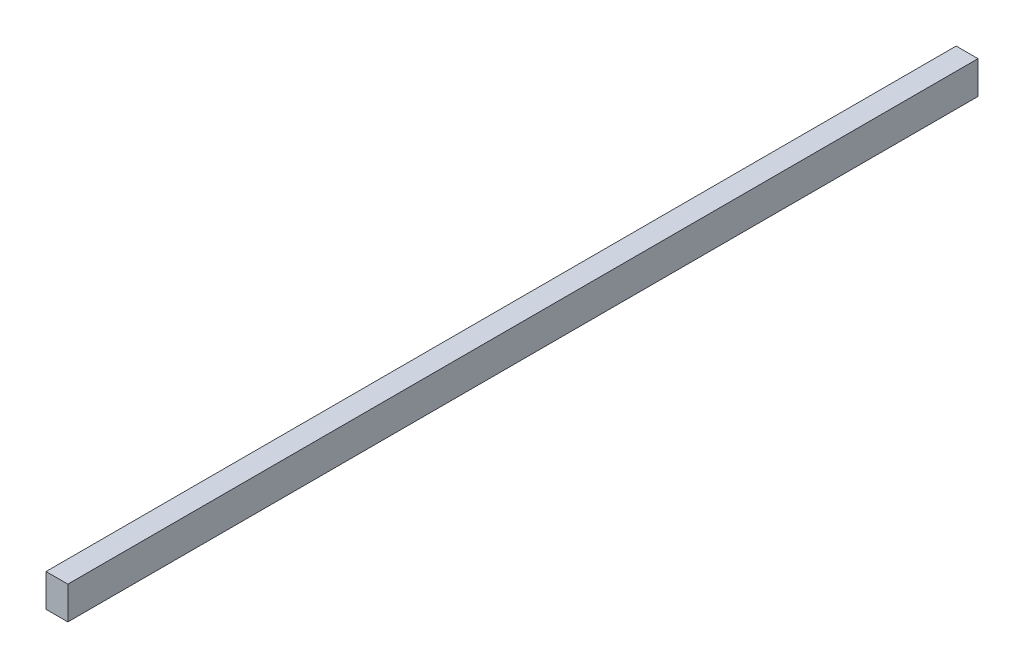
SolidWorks part; units mm, degrees
ref_plane "Front Plane" through (0, 0, 0) normal (0, 0, 1) x (1, 0, 0)
ref_plane "Top Plane" through (0, 0, 0) normal (0, 1, 0) x (1, 0, 0)
ref_plane "Right Plane" through (0, 0, 0) normal (1, 0, 0) x (0, 0, -1)
sketch "Sketch1" plane through (0, 0, 0) normal (1, 0, 0) x (0, 0, -1)
  line L1 (0, 0) -> (500, 0)
  line L2 (0, 0) -> (0, 18)
  line L3 (0, 18) -> (500, 18)
  line L4 (500, 0) -> (500, 18)
  dimension "D1" = 500
  dimension "D2" = 18
extrude "Boss-Extrude1" add sketch "Sketch1" along normal blind 12
